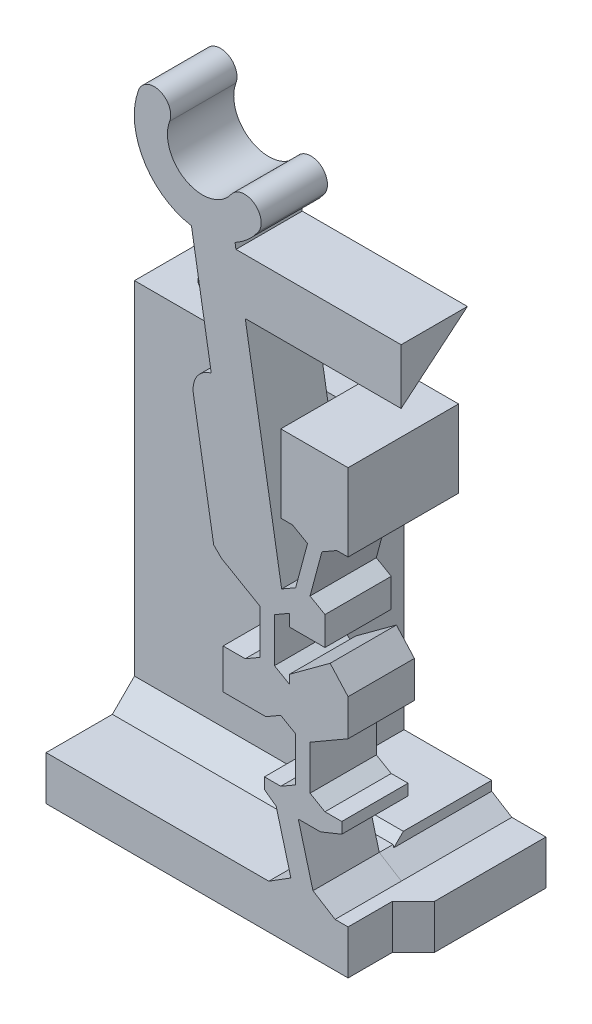
SolidWorks part; units mm, degrees
material "Nylon 6/12"
ref_plane "Front Plane" through (0, 0, 0) normal (0, 0, 1) x (1, 0, 0)
ref_plane "Top Plane" through (0, 0, 0) normal (0, 1, 0) x (1, 0, 0)
ref_plane "Right Plane" through (0, 0, 0) normal (1, 0, 0) x (0, 0, -1)
sketch "Sketch-SkeletonConfigUp" plane through (0, 0, 0) normal (0, 0, 1) x (1, 0, 0)
  line L0 (0, 0) -> (0, -50000) construction
  line L1 (0, 0) -> (4.5811, 6.2164) construction
  line L2 (9.8143, 13.3177) -> (4.5811, 13.945) construction
  line L3 (4.5811, 13.945) -> (2.9713, 10.4094) construction
  line L4 (2.9713, 10.4094) -> (4.5811, 6.2164) construction
  line L5 (4.5811, 13.945) -> (6.2429, 19.1409) construction
  line L6 (2.9713, 10.4094) -> (0.0405, 27.8193) construction
  line L7 (4.5811, 6.2164) -> (9.8143, 13.3177) construction
  line L8 (-587.3593, -797.0242) -> (9.8143, 13.3177) construction
  dimension "D2" = 7.7221
  dimension "D3" = 8.8212
  dimension "D4" = 5.2707
  dimension "D5" = 119.553
  dimension "D6" = 3.8848
  dimension "D7" = 5.4552
  dimension "D8" = 17.6549
  dimension "D9" = 4.4914
  dimension "D10" = 6.745
  dimension "D11" = 145.964
  dimension "D12" = 143.612
sketch "Sketch-SkeletonConfigDown" plane through (0, 0, 0) normal (0, 0, 1) x (1, 0, 0)
  line L0 (0, 0) -> (0, -50000) construction
  line L1 (0, 0) -> (4.5811, 6.2164) construction
  line L2 (9.8143, 13.3177) -> (4.5811, 13.945) construction
  line L3 (4.5811, 13.945) -> (6.1909, 10.4094) construction
  line L4 (6.1909, 10.4094) -> (4.5811, 6.2164) construction
  line L5 (4.5811, 13.945) -> (1.753, 18.6098) construction
  line L6 (6.1909, 10.4094) -> (-8.8652, 19.6294) construction
  line L7 (4.5811, 6.2164) -> (9.8143, 13.3177) construction
  line L8 (-589.9357, -800.5203) -> (9.8143, 13.3177) construction
  dimension "D2" = 7.7221
  dimension "D3" = 8.8212
  dimension "D4" = 5.2707
  dimension "D5" = 119.553
  dimension "D6" = 3.8848
  dimension "D7" = 5.4552
  dimension "D8" = 17.6549
  dimension "D9" = 4.4914
  dimension "D10" = 6.745
  dimension "D11" = 145.964
  dimension "D1" = 143.612
ref_plane "Plane-Cam Base" through (9.128, 0, 0) normal (1, 0, 0) x (0, 0, -1)
ref_plane "Plane-Down-to-Up Derailleur Clearance" through (6.628, 0, 0) normal (1, 0, 0) x (0, 0, -1)
ref_plane "Plane-Cam Cavity Roof" through (5.128, 0, 0) normal (1, 0, 0) x (0, 0, -1)
sketch "Sketch-SwitchBossUp" plane through (0, 0, 0) normal (0, 0, 1) x (1, 0, 0)
  line L0 (3.5811, 11.4759) -> (3.5811, 12.945) construction
  line L5 (5.5811, 12.5552) -> (5.5811, 11.263)
  line L7 (1.5115, 25.1048) -> (1.5536, 24.8548)
  line L8 (-0.4607, 24.7728) -> (0.4359, 19.4465)
  line L9 (2.9713, 10.4094) -> (0.0405, 27.8193) construction
  line L11 (0.1364, 21.2256) -> (2.1086, 21.5576) construction
  line L15 (6.628, -23.7286) -> (6.628, 23.7286) construction
  line L16 (2.9713, 10.4094) -> (4.5811, 6.2164) construction
  line L17 (3.5811, 12.945) -> (3.5811, 14.945) construction
  line L18 (5.5811, 12.945) -> (5.5811, 14.945) construction
  line L19 (4.2561, 13.945) -> (4.9061, 13.945) construction
  line L20 (3.5811, 14.945) -> (5.5811, 14.945) construction
  line L21 (3.5811, 12.945) -> (5.5811, 12.945) construction
  line L22 (4.5811, 12.945) -> (4.5811, 14.945) construction
  line L23 (4.5811, 6.2164) -> (8.5405, 7.1023) construction
  line L24 (1.9713, 9.4094) -> (1.9713, 11.4094) construction
  line L25 (3.9713, 9.4094) -> (3.9713, 11.4094) construction
  line L26 (3.9713, 9.4094) -> (1.9713, 9.4094) construction
  line L27 (1.9713, 11.4094) -> (3.9713, 11.4094) construction
  line L28 (3.5811, 7.2164) -> (5.5811, 7.2164) construction
  line L29 (3.5811, 7.2164) -> (3.5811, 5.2164) construction
  line L30 (5.5811, 7.2164) -> (5.5811, 5.2164) construction
  line L31 (3.5811, 5.2164) -> (5.5811, 5.2164) construction
  line L32 (4.9061, 6.2164) -> (4.2561, 6.2164) construction
  line L40 (3.2963, 10.4094) -> (2.6463, 10.4094) construction
  line L66 (0.0405, 27.8193) -> (0.0405, 50027.8193) construction
  line L74 (0.5455, 12.7717) -> (-0.3728, 18.2264)
  line L75 (0.3841, 13.7302) -> (2.3564, 14.0622) construction
  line L76 (5.5811, 11.263) -> (5.5811, 12.5552) construction
  line L77 (5.5811, 7.6061) -> (6.628, 8.2105)
  line L80 (5.8152, 10.763) -> (6.628, 9.8603)
  line L81 (9.128, 1033.2419) -> (9.128, 20.0586) construction
  line L85 (6.9307, 9.5241) -> (8.5405, 7.7363) construction
  line L88 (5.7256, 18.8347) -> (6.628, 18.8347)
  line L92 (3.7762, 8.3129) -> (6.9307, 9.5241) construction
  line L98 (1.9713, 9.0197) -> (0.9713, 9.0197)
  line L99 (0.9713, 9.0197) -> (0.9713, 7.2164)
  line L100 (0.9713, 7.2164) -> (2.9061, 7.2164)
  line L101 (4.5811, 6.2164) -> (6.9307, 9.5241) construction
  line L103 (0.0405, 27.8193) -> (1.9448, 26.4638) construction
  line L104 (6.9307, 9.5241) -> (8.5405, 7.7363) construction
  line L107 (1.9713, 9.4094) -> (1.9713, 9.0197) construction
  line L109 (0.0405, 27.8193) -> (-2.1498, 28.6358) construction
  line L111 (6.628, 9.8603) -> (6.628, 8.2105)
  line L112 (6.628, 9.8603) -> (6.9307, 9.5241) construction
  line L113 (2.8424, 4.8267) -> (2.8424, 4.3267)
  line L114 (7.3693, 7.7363) -> (7.3563, 7.7363) construction
  line L121 (5.0383, -1.1653) -> (5.0383, 1.4614) construction
  line L127 (5.5811, 15.3347) -> (5.5811, 14.945) construction
  line L130 (6.0388, 0.837) -> (6.628, 0.837)
  line L132 (2.8424, 4.3267) -> (3.3749, 3.937)
  line L133 (2.9713, 10.4094) -> (6.1909, 10.4094) construction
  line L134 (4.5811, 10.4094) -> (4.5811, 13.945) construction
  line L135 (4.5811, 10.4094) -> (4.5811, 6.2164) construction
  line L136 (0.8973, 12.4192) -> (0.5455, 12.7717)
  line L137 (3.9713, 9.4094) -> (5.5811, 7.2164) construction
  line L139 (5.8152, 10.763) -> (3.9713, 9.4094)
  line L141 (4.0386, 1.4604) -> (3.0388, 0.8347)
  line L142 (3.0388, 0.8347) -> (3.0388, -1.1653)
  line L143 (9.128, 20.0586) -> (9.128, 18.3333) construction
  line L145 (9.128, 16.6071) -> (9.128, -49992.4167) construction
  line L147 (5.5811, 11.263) -> (5.5811, 12.5552) construction
  line L150 (3.0388, -1.1653) -> (5.0383, -1.1653)
  line L151 (3.3749, 3.937) -> (4.3749, 3.937) construction
  line L152 (4.792, 14.945) -> (4.2561, 12.945)
  line L153 (5.442, 14.945) -> (4.9061, 12.945)
  line L157 (3.5811, 18.8347) -> (3.5811, 15.3347)
  line L158 (6.117, 15.3347) -> (6.628, 15.3347)
  line L162 (3.2963, 11.4094) -> (3.2963, 9.4094)
  line L164 (2.6463, 11.4094) -> (2.6463, 9.4094)
  line L169 (4.2561, 7.2164) -> (4.2561, 5.2164)
  line L170 (4.9061, 5.2164) -> (4.9061, 7.2164)
  line L175 (4.2561, 7.2164) -> (3.5811, 7.6061)
  line L176 (4.9061, 7.2164) -> (5.5811, 7.6061)
  line L177 (5.5811, 7.2164) -> (5.5811, 7.6061) construction
  line L179 (4.2561, 5.2164) -> (3.5811, 4.8267)
  line L180 (3.5811, 5.2164) -> (3.5811, 4.8267) construction
  line L181 (3.5811, 4.8267) -> (2.8424, 4.8267)
  line L183 (4.9061, 5.2164) -> (5.5811, 4.8267)
  line L184 (5.5811, 5.2164) -> (5.5811, 4.8267) construction
  line L186 (9.128, -23.7286) -> (9.128, 23.7286) construction
  line L187 (2.6463, 9.4094) -> (1.9713, 9.0197)
  line L188 (3.2963, 9.4094) -> (3.9713, 9.0197)
  line L189 (3.2963, 11.4094) -> (3.9713, 11.7991)
  line L190 (2.6463, 11.4094) -> (0.8973, 12.4192)
  line L191 (3.9713, 11.4094) -> (3.9713, 11.7991) construction
  line L192 (3.9713, 11.7991) -> (3.9713, 11.263)
  line L193 (4.9061, 12.945) -> (5.5811, 12.5552)
  line L194 (4.2561, 12.945) -> (3.6203, 12.5779)
  line L195 (3.9713, 11.263) -> (5.5811, 11.263)
  line L196 (3.9713, 9.4094) -> (3.9713, 9.0197)
  line L197 (3.5811, 7.2164) -> (3.5811, 7.6061) construction
  line L199 (3.5811, 7.6061) -> (2.9061, 7.2164)
  line L201 (2.8424, 4.3267) -> (2.8424, 3.937) construction
  line L202 (2.8424, 3.937) -> (3.3749, 3.937) construction
  line L204 (5.0383, 1.437) -> (3.0388, 1.437) construction
  line L205 (3.0388, 1.437) -> (3.0388, 0.8347) construction
  line L206 (5.0383, 1.4614) -> (6.0388, 0.837)
  line L207 (9.128, 18.3333) -> (9.128, 16.6071) construction
  line L208 (6.628, -1.1653) -> (6.628, 0.837)
  line L209 (9.128, 20.0586) -> (9.128, 16.6071) construction
  line L211 (5.0383, 1.4614) -> (4.3749, 3.937)
  line L212 (4.0386, 1.4604) -> (3.3749, 3.937)
  line L214 (4.792, 14.945) -> (4.1169, 15.3347)
  line L215 (4.1169, 15.3347) -> (3.5811, 15.3347)
  line L216 (5.442, 14.945) -> (6.117, 15.3347)
  line L217 (5.5811, 12.945) -> (5.5811, 12.5552) construction
  line L218 (5.442, 14.945) -> (5.442, 15.3347) construction
  line L219 (6.117, 15.3347) -> (4.1169, 15.3347) construction
  line L221 (9.028, 22.3548) -> (9.028, 24.8548)
  line L224 (3.5811, 18.8347) -> (5.7256, 18.8347)
  line L232 (6.628, 15.3347) -> (6.628, 18.8347)
  line L233 (6.628, -1.1653) -> (5.0383, -1.1653)
  line L236 (1.5536, 24.8548) -> (9.028, 24.8548)
  line L240 (4.3749, 3.937) -> (5.3749, 3.937)
  line L241 (5.3749, 3.937) -> (6.3424, 4.3267)
  line L248 (9.028, 22.3548) -> (1.9744, 22.3548)
  line L249 (1.9744, 22.3548) -> (3.6203, 12.5779)
  line L367 (5.5811, 4.8267) -> (6.3424, 4.8267)
  line L368 (6.3424, 4.8267) -> (6.3424, 4.3267)
  arc A0 (1.5115, 25.1048) -> (2.5558, 26.0289) centre (0.0405, 27.8193) ccw
  arc A1 (-0.4607, 24.7728) -> (-2.8525, 28.8978) centre (0.0405, 27.8193) cw
  arc A2 (-2.8525, 28.8978) -> (-1.447, 28.3738) centre (-2.1498, 28.6358) cw
  arc A3 (2.5558, 26.0289) -> (1.3338, 26.8987) centre (1.9448, 26.4638) ccw
  arc A4 (-1.447, 28.3738) -> (1.3338, 26.8987) centre (0.0405, 27.8193) ccw
  arc A5 (3.5811, 12.945) -> (3.5811, 14.945) centre (3.1778, 13.945) ccw construction
  arc A6 (5.5811, 12.945) -> (5.5811, 14.945) centre (5.9843, 13.945) cw construction
  arc A7 (2.5293, 9.921) -> (1.9713, 11.4094) centre (1.568, 10.4094) ccw construction
  arc A8 (3.9713, 11.4094) -> (3.9713, 9.4094) centre (4.3745, 10.4094) ccw construction
  arc A9 (3.5811, 7.2164) -> (3.5811, 5.2164) centre (3.1779, 6.2164) cw construction
  arc A10 (5.5811, 7.2164) -> (5.5811, 5.2164) centre (5.9844, 6.2164) ccw construction
  arc A19 (-0.3728, 18.2264) -> (0.4359, 19.4465) centre (0.6836, 18.4042) cw
  circle A28 centre (0.0405, 27.8193) radius 2.3375 construction
  arc A29 (1.9713, 9.4094) -> (2.5293, 9.921) centre (1.568, 10.4094) ccw construction
  point P7 (3.5811, 12.6384)
  point P53 (4.5811, 13.945)
  point P63 (2.9713, 10.4094)
  point P93 (1.1225, 21.3916)
  dimension "D23" = 1.5875
  dimension "D24" = 0.75
  dimension "D2" = 2
  dimension "D5" = 2
  dimension "D6" = 0.65
  dimension "D8" = 42
  dimension "D16" = 42
  dimension "D27" = 120
  dimension "D28" = 120
  dimension "D29" = 120
  dimension "D30" = 120
  dimension "D31" = 120
  dimension "D32" = 120
  dimension "D33" = 120
  dimension "D34" = 120
  dimension "D17" = 0.5
  dimension "D21" = 3.5
  dimension "D22" = 1
  dimension "D38" = 2
  dimension "D39" = 0.5
  dimension "D40" = 60
  dimension "D41" = 1
  dimension "D42" = 45
  dimension "D43" = 120
  dimension "D10" = 15
  dimension "D12" = 2.5
  dimension "D13" = 1
  dimension "D19" = 1
  dimension "D25" = 15
  dimension "D26" = 120
  dimension "D35" = 120
  dimension "D20" = 3
  dimension "D48" = 2
  dimension "D49" = 0.6
  dimension "D82" = 1
  dimension "D83" = 3.5
  dimension "D14" = 2.5
  dimension "D15" = 0.25
extrude "Boss-Switch Body" add sketch "Sketch-SwitchBossUp" along normal blind 3
sketch "Sketch1" plane through (0, 0, 0) normal (0, 0, -1) x (-1, 0, 0)
  line L1 (-7.5811, -1.1653) -> (0.4122, -1.1653)
  line L2 (-7.5811, -1.1653) -> (-7.5811, 0.837)
  line L4 (0.4122, -1.1653) -> (0.4122, 0.8347)
  line L5 (-3.5811, 18.8347) -> (-7.5811, 18.8347)
  line L10 (-7.5811, 18.8347) -> (-7.5811, 15.3347)
  line L11 (-4.0386, 1.4604) -> (-5.0386, 1.4604)
  line L12 (-7.5811, 15.3347) -> (-3.5811, 15.3347)
  line L13 (-4.0386, 1.4604) -> (-3.0388, 0.8347)
  line L14 (-3.5811, 15.3347) -> (-3.5811, 18.8347)
  line L20 (-4.3749, 3.937) -> (-5.0383, 1.4614) construction
  line L22 (-3.0388, -1.1653) -> (-6.628, -1.1653) construction
  line L23 (-3.0388, 0.8347) -> (0.4122, 0.8347)
  line L24 (-5.0386, 1.4604) -> (-6.0388, 0.837)
  line L25 (-6.0388, 0.837) -> (-7.5811, 0.837)
  dimension "D1" = 3.5
extrude "Boss-Flange Width" add sketch "Sketch1" along normal blind 5
ref_plane "Plane-Sta2Sit Groove" through (0.0405, 0, 0) normal (1, 0, 0) x (0, 0, -1)
ref_plane "Plane-Cam Outer Surface" through (-12.0395, 0, 0) normal (1, 0, 0) x (0, 0, -1)
ref_plane "Plane-FlangeTop" through (-7.0395, 0, 0) normal (1, 0, 0) x (0, 0, -1)
sketch "Sketch2" plane through (-7.0395, 0, 0) normal (1, 0, 0) x (0, 0, -1)
  line L0 (5, 15.3347) -> (-3, 15.3347) construction
  line L1 (5, 17.3347) -> (1, 17.3347)
  line L2 (5, 17.3347) -> (5, 15.3347)
  line L3 (5, 15.3347) -> (1, 15.3347)
  line L4 (1, 17.3347) -> (1, 15.3347)
  line L5 (-3, -1.1653) -> (-3, 0.837) construction
  line L11 (5, 0.8347) -> (-3, 0.8347)
  line L12 (5, 0.8347) -> (5, -1.1653)
  line L13 (5, -1.1653) -> (-3, -1.1653)
  line L14 (-3, 0.8347) -> (-3, -1.1653)
  line L15 (0, 10.4094) -> (0, 27.8193) construction
  line L17 (5, 0.837) -> (5, -1.1653) construction
  line L18 (-3, 0.8347) -> (0, 0.8347) construction
  dimension "D1" = 1
  dimension "D2" = 2
extrude "Boss-Flange Height" add sketch "Sketch2" along normal up to surface (11.6675 mm away)
sketch "Sketch10" plane through (0, 15.3347, 0) normal (0, 1, 0) x (1, 0, 0)
  line L0 (9.128, -23.7286) -> (9.128, 23.7286) construction
  line L1 (7.5811, 5) -> (5.128, 5)
  line L2 (7.5811, 5) -> (7.5811, 2)
  line L3 (7.5811, 2) -> (5.128, 2)
  line L5 (4.628, 7) -> (4.628, 1) construction
  line L6 (3.5811, 1) -> (-7.0395, 1) construction
  line L8 (5.128, 5) -> (5.128, 2)
  dimension "D1" = 1
  dimension "D2" = 0.5
  dimension "D3" = 4.5
extrude "Cut-Up-To-Down Derailleur Clearance" cut sketch "Sketch10" along normal up to next
sketch "Sketch17" plane through (0, 15.3347, 0) normal (0, -1, 0) x (1, 0, 0)
  line L0 (5.128, -5) -> (-7.0395, -5)
  line L1 (5.128, -5) -> (-7.0395, -5) construction
  line L2 (-7.0395, -5) -> (-7.0395, -1)
  line L3 (-7.0395, -1) -> (5.128, -1)
  line L4 (5.128, -1) -> (5.128, -5)
  line L5 (-7.0395, -1) -> (-7.0395, -5) construction
extrude "Boss-Flange Support" add sketch "Sketch17" along normal up to surface (14.5 mm away) up to face at (-2.0003, 0.8347, -1)
sketch "Sketch-HolePositions" plane through (0, -1.1653, 0) normal (0, -1, 0) x (1, 0, 0)
  line L0 (-7.0395, -3) -> (7.5811, -3) construction
  line L1 (7.5811, -5) -> (-7.0395, -5) construction
  line L2 (7.5811, -5) -> (7.5811, 0) construction
  line L4 (-7.0395, -22.2167) -> (-7.0395, 22.2167) construction
  point P6 (-5.0395, -3)
  point P7 (-0.5395, -3)
  dimension "D1" = 2
  dimension "D2" = 4.5
  dimension "D3" = 2
sketch "Sketch6" plane through (0, -1.1653, 0) normal (0, -1, 0) x (-1, 0, 0)
  point P0 (5.0395, 3)
  point P3 (0.5395, 3)
hole_wizard "Tap Drill for M2x0.4 Tap1" positions "Sketch6" profile "Sketch5" hole size "M2x0.4" standard "ANSI Metric" end condition through all
sketch "Sketch5" plane through (-5.0395, -1.1653, -3) normal (1, 0, 0) x (0, 0, -1)
  line L0 (0, 0) -> (0, 30.5511)
  line L1 (0, 30.5511) -> (0.8, 30.5511)
  line L2 (0.8, 30.5511) -> (0.8, 0)
  line L5 (0.8, 0) -> (0, 0)
  line L11 (0, -6.35) -> (0, 107.95) construction
  dimension "Thru Hole Dia." = 1.6
  dimension "Thru Hole Depth" = 30.5511
sketch "Sketch9" plane through (0, -1.1653, 0) normal (0, -1, 0) x (1, 0, 0)
  point P0 (-5.0395, -3)
  point P3 (-0.5395, -3)
hole_wizard "M2 Clearance Hole2" positions "Sketch9" profile "Sketch8" hole size "M2" standard "ANSI Metric"
sketch "Sketch8" plane through (-5.0395, -1.1653, -3) normal (1, 0, 0) x (0, 0, -1)
  line L0 (0, 0) -> (0, 15.721)
  line L1 (0, 15.721) -> (1.2, 15)
  line L2 (1.2, 15) -> (1.2, 0)
  line L5 (1.2, 0) -> (0, 0)
  line L10 (0, 15.721) -> (-1.2, 15) construction
  line L11 (0, -6.35) -> (0, 107.95) construction
  dimension "Hole Dia." = 2.4
  dimension "Hole Depth" = 15
  dimension "Drill Angle" = 118
sketch "Sketch-Measurements for Derailleur Ramps" [suppressed] plane through (0, 0, 0) normal (0, 0, 1) x (1, 0, 0)
  line L0 (3.184, 15.1695) -> (2.4687, 19.4188)
  line L1 (2.8264, 17.2941) -> (1.8402, 17.1281)
  line L2 (2.9713, 10.4094) -> (0.0405, 27.8193) construction
  line L3 (1.8402, 17.1281) -> (-1.3081, 15.0016)
  line L4 (6.1909, 10.4094) -> (-8.8652, 19.6294) construction
  line L5 (1.8402, 17.1281) -> (2.6012, 12.6077)
  line L6 (2.6012, 12.6077) -> (-1.3081, 15.0016)
  line L7 (0.2661, 16.0649) -> (0.2661, 17.1281)
  line L8 (0.2661, 17.1281) -> (1.8402, 17.1281)
  line L9 (6.1909, 10.4094) -> (2.9713, 10.4094)
  line L10 (5.386, 8.3129) -> (3.7762, 8.3129)
  line L11 (2.6116, 18.5698) -> (1.5115, 25.1048) construction
  line L12 (6.1909, 10.4094) -> (4.5811, 6.2164) construction
  line L13 (4.5811, 8.3129) -> (4.5811, 8.7912)
  line L14 (4.5811, 6.2164) -> (5.386, 8.3129)
  line L15 (2.9713, 10.4094) -> (4.5811, 6.2164) construction
  line L16 (3.7762, 8.3129) -> (4.5811, 6.2164)
  line L17 (5.386, 8.3129) -> (5.386, 8.7912)
  dimension "D1" = 1.5742
  dimension "D2" = 0.8049
ref_plane "Plane1" through (0, 7.1023, 0) normal (0, 1, 0) x (1, 0, 0)
ref_plane "Plane-Cantilever Cut" [suppressed] through (7.0848, 8.5204, -1.9058) normal (-0.6301, -0.7578, 0.1695) x (-0.7765, 0.6151, -0.1368)
sketch "Sketch14" [suppressed] plane through (7.0848, 8.5204, -1.9058) normal (-0.6301, -0.7578, 0.1695) x (-0.7765, 0.6151, -0.1368)
  line L0 (2.3023, -1.6911) -> (-0.3551, -1.6911)
  line L2 (2.3023, -4.3362) -> (2.3023, -1.6911)
  line L3 (-0.3551, -1.6911) -> (-0.3551, -4.4608)
  line L5 (-0.3551, -4.4608) -> (1.0087, -5.0843)
  line L6 (1.0087, -5.0843) -> (2.3023, -4.3362)
extrude "Cut-Down-to-Up Cantilever Slope" [suppressed] cut sketch "Sketch14" against normal up to next
ref_plane "Plane-Symmetry Plane" through (0, 0, 1.5) normal (0, 0, 1) x (1, 0, 0)
sketch "Sketch-Cable Center Point" plane through (0, 0, 1.5) normal (0, 0, 1) x (1, 0, 0)
  line L0 (0.0405, 27.8193) -> (0.1722, 27.0366)
  line L1 (2.9713, 10.4094) -> (0.0405, 27.8193) construction
  point P0 (0.0405, 27.8193)
  dimension "D1" = 0.7937
chamfer "Chamfer-Flange Support" distance 1.5 angle 45 1 edges at (3.5811, 17.3347, -3)
chamfer "Chamfer-Flange Support 2" distance 1.5 angle 45 2 edges at (5.128, 17.0847, -2) (5.128, 15.3347, -1.5)
chamfer "Chamfer-Flange Support 3" distance 1 angle 45 1 edges at (-2.0003, 0.8347, -1)
chamfer "Chamfer7" [suppressed] distance 1 angle 45
sketch "Sketch23" plane through (0, 0, -1) normal (0, 0, 1) x (1, 0, 0)
  line L0 (5.128, 1.8347) -> (1.1605, 1.8347)
  line L1 (-7.0395, 1.8347) -> (5.128, 1.8347) construction
  line L2 (1.1605, 1.8347) -> (1.1605, 13.8347)
  line L3 (1.1605, 13.8347) -> (5.128, 13.8347)
  line L4 (5.128, 13.8347) -> (5.128, 1.8347)
  line L5 (0.6605, -1.1653) -> (0.6605, 13.8347) construction
  dimension "D1" = 0.5
extrude "Cut-Gap for Printing" cut sketch "Sketch23" against normal through all
sketch "Sketch25" plane through (0, 0, 0) normal (0, 0, 1) x (1, 0, 0)
  line L0 (6.628, 15.3347) -> (7.5811, 15.3347)
  line L1 (7.5811, 15.3347) -> (7.5811, 18.8347)
  line L2 (7.5811, 18.8347) -> (6.628, 18.8347)
  line L3 (6.628, -23.7286) -> (6.628, 23.7286) construction
  line L4 (7.5811, 18.8347) -> (3.5811, 18.8347) construction
  line L5 (6.628, 18.8347) -> (6.628, 15.3347)
  line L6 (7.5811, 18.8347) -> (7.5811, 15.3347) construction
  point P4 (0, 0)
  point P12 (7.5811, 18.8347)
extrude "Cut-Derailleur Clearance" cut sketch "Sketch25" against normal through all
chamfer "Chamfer8" distance 1 angle 45 1 edges at (6.628, -0.1641, 0)
ref_plane "Plane2" through (-5.9548, 8.4004, 7.0004) normal (0.4783, -0.6747, -0.5622) x (-0.8782, -0.3674, -0.3062)
sketch "Sketch26" plane through (-5.9548, 8.4004, 7.0004) normal (0.4783, -0.6747, -0.5622) x (-0.8782, -0.3674, -0.3062)
  line L0 (-12.9549, 15.9117) -> (-12.9549, 12.0065)
  line L1 (-17.0603, 15.9117) -> (-10.4961, 15.9117) construction
  line L2 (-10.8657, 12.0065) -> (-17.0603, 12.0065) construction
  line L3 (-12.9549, 12.0065) -> (-20.0302, 12.0065)
  line L4 (-20.0302, 12.0065) -> (-20.0302, 15.9117)
  line L5 (-20.0302, 15.9117) -> (-12.9549, 15.9117)
extrude "Cut-Extrude1" cut sketch "Sketch26" along normal up to next
sketch "Sketch27" plane through (5.128, 0, 0) normal (1, 0, 0) x (0, 0, -1)
  line L0 (3.5, 18.8347) -> (3.5, 13.8347) construction
  line L1 (3, 18.8347) -> (5, 18.8347)
  line L2 (3, 18.8347) -> (3, 13.8347)
  line L3 (3, 13.8347) -> (5, 13.8347)
  line L4 (5, 18.8347) -> (5, 13.8347)
  dimension "D1" = 0.5
extrude "Cut-Wide Derailleur Clearance" cut sketch "Sketch27" against normal blind 4 and the other way through all
chamfer "Chamfer9" distance 1 angle 45 1 edges at (4.6045, 18.8347, -3)
equation "\"axle-diameter\"=2"
equation "\"switch-thickness\"=12"
equation "\"base-width\"=4.0"
equation "\"axle-bushing-radius\"=3"
equation "\"clearance\"= 0.25"
equation "\"arm-width\"=1.5"
equation "\"min-diameter\"=70"
equation "\"alpha\"=143.6120"
equation "\"gamma\"=119.5526"
equation "\"delta\"=145.9637"
equation "\"epsilon\"=6.7452"
equation "\"l_AB\"=8.8212"
equation "\"l_AC\"=4.4914"
equation "\"l_BD\"=5.2707"
equation "\"l_CD\"=3.8848"
equation "\"l_CE\"=17.6549"
equation "\"l_DF\"=5.4552"
equation "\"l_OA\"=7.7221"
equation "\"D2@Sketch-SkeletonConfigUp\" = \"l_OA\""
equation "\"D3@Sketch-SkeletonConfigUp\" = \"l_AB\""
equation "\"D4@Sketch-SkeletonConfigUp\" = \"l_BD\""
equation "\"D5@Sketch-SkeletonConfigUp\" = \"gamma\""
equation "\"D6@Sketch-SkeletonConfigUp\" = \"l_CD\""
equation "\"D7@Sketch-SkeletonConfigUp\" = \"l_DF\""
equation "\"D8@Sketch-SkeletonConfigUp\" = \"l_CE\""
equation "\"D9@Sketch-SkeletonConfigUp\" = \"l_AC\""
equation "\"D_groove\"=3.175"
equation "\"D7@Sketch-SkeletonConfigDown\" = \"l_DF\""
equation "\"D6@Sketch-SkeletonConfigDown\" = \"l_CD\""
equation "\"D2@Sketch-SkeletonConfigDown\" = \"l_OA\""
equation "\"D3@Sketch-SkeletonConfigDown\" = \"l_AB\""
equation "\"D9@Sketch-SkeletonConfigDown\" = \"l_AC\""
equation "\"D8@Sketch-SkeletonConfigDown\" = \"l_CE\""
equation "\"D5@Sketch-SkeletonConfigDown\" = \"gamma\""
equation "\"D4@Sketch-SkeletonConfigDown\" = \"l_BD\""
equation "\"D1@Sketch-SkeletonConfigDown\" = \"alpha\""
equation "\"hinge_length\"=1.5"
equation "\"hinge_depth\"=0.25"
equation "\"D10@Sketch-SkeletonConfigUp\"=\"epsilon\""
equation "\"D11@Sketch-SkeletonConfigUp\"=\"delta\""
equation "\"D12@Sketch-SkeletonConfigUp\"=\"alpha\""
equation "\"D11@Sketch-SkeletonConfigDown\"=\"delta\""
equation "\"D10@Sketch-SkeletonConfigDown\"=\"epsilon\""
equation "\"EE_dx\"=8.9056"
equation "\"EE_dy\"=8.1898"
equation "\"r_groove\"=\"D_groove\"/2"
equation "\"t_wall\"=25.4/16"
equation "\"width_lower\"=\"D_groove\"+\"t_wall\""
equation "\"cable_to_bottom\"=30.6257"
equation "\"switch_EE-up_base_dy\"=24"
equation "\"switch_EE-down_base_dy\"=16"
equation "\"D_axle\"=25.4/8"
equation "\"D_up_to_down\"=16"
equation "\"D_down_to_up\"=25"
equation "\"t_cam_base\"=7.5"
equation "\"D23@Sketch-SwitchBossUp\"=\"D_groove\"/2"
equation "\"D1@Sketch-Cable Center Point\"=\"D_groove\"/4"
